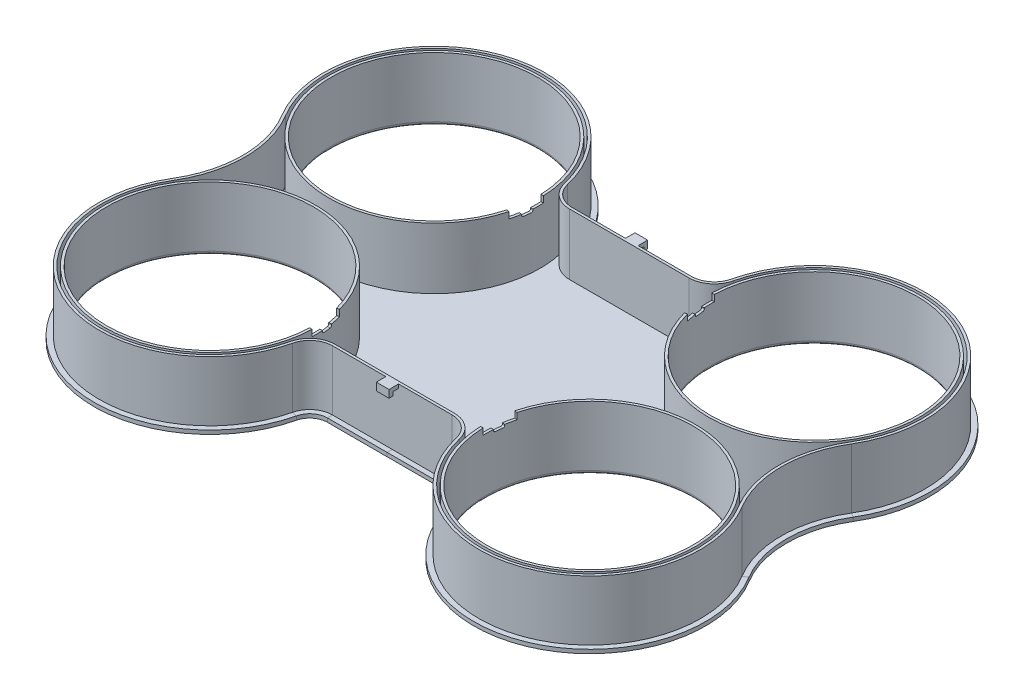
SolidWorks part; units mm, degrees
ref_plane "Front Plane" through (0, 0, 0) normal (0, 0, 1) x (1, 0, 0)
ref_plane "Top Plane" through (0, 0, 0) normal (0, 1, 0) x (1, 0, 0)
ref_plane "Right Plane" through (0, 0, 0) normal (1, 0, 0) x (0, 0, -1)
sketch "Sketch1" plane through (0, 0, 0) normal (0, 1, 0) x (1, 0, 0)
  line L0 (-1000, 0) -> (49000, 0) construction
  line L1 (0, -1000) -> (0, 49000) construction
  line L2 (-23.3898, 47) -> (23.3898, 47)
  line L3 (-23.3898, -47) -> (23.3898, -47)
  arc A0 (111.7183, 21.4824) -> (32.1516, 53.9429) centre (74.5, 44) ccw
  arc A1 (111.7183, 21.4824) -> (111.7183, -21.4824) centre (147.2255, 0) ccw
  arc A2 (23.3898, 47) -> (32.1516, 53.9429) centre (23.3898, 56) ccw
  arc A5 (-23.3898, 47) -> (-32.1516, 53.9429) centre (-23.3898, 56) cw
  arc A6 (-111.7183, 21.4824) -> (-111.7183, -21.4824) centre (-147.2255, 0) cw
  arc A7 (-111.7183, 21.4824) -> (-32.1516, 53.9429) centre (-74.5, 44) cw
  arc A8 (-111.7183, -21.4824) -> (-32.1516, -53.9429) centre (-74.5, -44) ccw
  arc A9 (-23.3898, -47) -> (-32.1516, -53.9429) centre (-23.3898, -56) ccw
  arc A12 (23.3898, -47) -> (32.1516, -53.9429) centre (23.3898, -56) cw
  arc A13 (111.7183, -21.4824) -> (32.1516, -53.9429) centre (74.5, -44) cw
  point P9 (0, -47)
  point P22 (0, 47)
  dimension "D1" = 87
  dimension "D2" = 236
  dimension "D3" = 175
  dimension "D4" = 41.5
  dimension "D5" = 9
  dimension "D6" = 47
extrude "Base" add sketch "Sketch1" along normal blind 25
sketch "Sketch3" plane through (0, 25, 0) normal (0, 1, 0) x (1, 0, 0)
  line L0 (-1000, 0) -> (49000, 0) construction
  line L1 (0, -1000) -> (0, 49000) construction
  circle A0 centre (74.5, 44) radius 40.5
  arc A2 (111.7183, 21.4824) -> (32.1516, 53.9429) centre (74.5, 44) ccw construction
  circle A3 centre (74.5, -44) radius 40.5
  circle A4 centre (-74.5, -44) radius 40.5
  circle A5 centre (-74.5, 44) radius 40.5
  dimension "D1" = 3
extrude "PropHoles" cut sketch "Sketch3" against normal blind 25
shell "Shell2" thickness 1 removed face at (-74.5, 25, -84.5)
sketch "Sketch4" plane through (0, 0, 0) normal (1, 0, 0) x (0, 0, -1)
  line L1 (-47, 0) -> (-49, 0)
  line L2 (-47, 0) -> (-47, 1.5)
  line L3 (-47, 1.5) -> (-49, 1.5)
  line L4 (-49, 0) -> (-49, 1.5)
  dimension "D1" = 1.5
  dimension "D2" = 2
sweep "Lip" add profiles "Sketch4" path "Sketch1<2>"
sketch "Sketch1<2>" plane through (0, 0, 0) normal (0, 1, 0) x (1, 0, 0) same geometry as "Sketch1"
sketch "Sketch5" plane through (0, 0, 0) normal (1, 0, 0) x (0, 0, -1)
  line L8 (-47, 25) -> (-50.75, 25)
  line L9 (-47, 25) -> (-53.9429, 25) construction
  line L10 (-50.75, 25) -> (-50.75, 22)
  line L11 (-50.75, 22) -> (-49.25, 22)
  line L12 (-49.25, 22) -> (-49.25, 23.5)
  line L13 (-49.25, 23.5) -> (-47, 23.5)
  line L14 (-47, 25) -> (-47, 1.5) construction
  line L15 (0, -1000) -> (0, 49000) construction
  line L16 (49.25, 23.5) -> (47, 23.5)
  line L17 (49.25, 22) -> (49.25, 23.5)
  line L18 (50.75, 22) -> (49.25, 22)
  line L19 (50.75, 25) -> (50.75, 22)
  line L20 (47, 25) -> (50.75, 25)
  line L21 (-47, 23.5) -> (-47, 25)
  line L22 (47, 23.5) -> (47, 25)
  dimension "D1" = 2.25
  dimension "D2" = 1.5
  dimension "D3" = 3
  dimension "D4" = 1.5
extrude "Hooks" add sketch "Sketch5" along normal mid plane 5
fillet "Fillet1" radius 1.5 4 edges at (-74.5, 0, -84.5) (74.5, 0, -3.5) (74.5, 0, 3.5) (-74.5, 0, 84.5)
sketch "Sketch6" plane through (0, 25, 0) normal (0, 1, 0) x (1, 0, 0)
  line L0 (74.5, -44) -> (34.4266, -33.2123)
  line L1 (74.5, -44) -> (33.0236, -45.4)
  line L2 (2.5, -47) -> (23.3898, -47) construction
  line L3 (-1000, 0) -> (49000, 0) construction
  line L4 (0, -1000) -> (0, 49000) construction
  line L5 (74.5, 44) -> (33.0236, 45.4)
  line L6 (74.5, 44) -> (34.4266, 33.2123)
  line L7 (-74.5, 44) -> (-34.4266, 33.2123)
  line L8 (-74.5, 44) -> (-33.0236, 45.4)
  line L9 (-74.5, -44) -> (-33.0236, -45.4)
  line L10 (-74.5, -44) -> (-34.4266, -33.2123)
  circle A0 centre (74.5, -44) radius 41.5 construction
  circle A1 centre (74.5, -44) radius 41.5 construction
  arc A2 (34.4266, -33.2123) -> (33.0236, -45.4) centre (74.5, -44) ccw
  arc A3 (34.4266, 33.2123) -> (33.0236, 45.4) centre (74.5, 44) cw
  arc A4 (-34.4266, 33.2123) -> (-33.0236, 45.4) centre (-74.5, 44) ccw
  arc A5 (-34.4266, -33.2123) -> (-33.0236, -45.4) centre (-74.5, -44) cw
  dimension "D1" = 17
  dimension "D2" = 1.6
extrude "ArmHoles" cut sketch "Sketch6" against normal blind 2.5
ref_plane "ArmDetail" through (38.7322, 0, 4.4587) normal (-0.9934, 0, -0.1144) x (-0.1144, 0, 0.9934)
sketch "Sketch7" plane through (38.7322, 0, 4.4587) normal (-0.9934, 0, -0.1144) x (-0.1144, 0, 0.9934)
  line L0 (41.1777, 22.5) -> (29.2052, 22.5) construction
  line L1 (36.6052, 21.5) -> (33.8052, 21.5)
  line L2 (37.2052, 22.1) -> (37.2052, 22.5)
  line L3 (37.2052, 22.5) -> (33.2052, 22.5)
  line L4 (33.2052, 22.1) -> (33.2052, 22.5)
  line L5 (29.2052, 25) -> (29.2052, 22.5) construction
  arc A0 (36.6052, 21.5) -> (37.2052, 22.1) centre (36.6052, 22.1) ccw
  arc A1 (33.8052, 21.5) -> (33.2052, 22.1) centre (33.8052, 22.1) cw
  dimension "D4" = 0.6
  dimension "D1" = 4
  dimension "D2" = 4
  dimension "D3" = 1
extrude "ArmDetailCut" cut sketch "Sketch7" along normal blind 2.5
mirror "ArmDetails" about plane through (0, 0, 0) normal (0, 0, 1) of "ArmDetailCut" second plane through (0, 0, 0) second plane normal (1, 0, 0)
